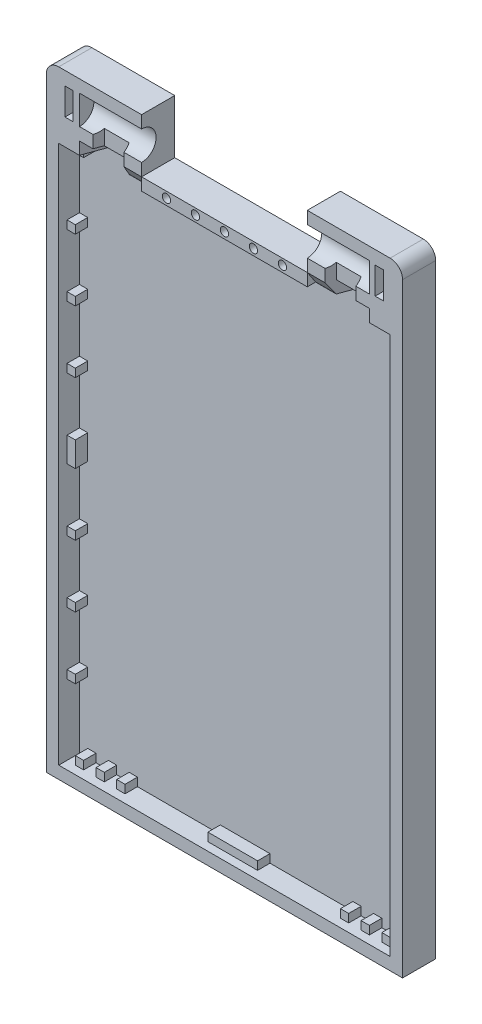
SolidWorks part; units mm, degrees
material "ABS"
ref_plane "Ön Düzlem" through (0, 0, 0) normal (0, 0, 1) x (1, 0, 0)
ref_plane "Üst Düzlem" through (0, 0, 0) normal (0, 1, 0) x (1, 0, 0)
ref_plane "Sağ Düzlem" through (0, 0, 0) normal (1, 0, 0) x (0, 0, -1)
sketch "Çizim1" plane through (0, 0, 0) normal (0, 0, 1) x (1, 0, 0)
  line L0 (-27.9937, 101.5335) -> (-27.9937, -28.4665)
  line L1 (-27.9937, 101.5335) -> (-22.9937, 101.5335)
  line L2 (52.0063, 101.5335) -> (52.0063, -28.4665)
  line L3 (-27.9937, -28.4665) -> (52.0063, -28.4665)
  line L4 (-30.9937, -31.4665) -> (55.0063, -31.4665)
  line L5 (55.0063, 104.5335) -> (55.0063, -31.4665)
  line L6 (-27.9937, 104.5335) -> (-22.9937, 104.5335)
  line L7 (-30.9937, 104.5335) -> (-30.9937, -31.4665)
  line L8 (-30.9937, 104.5335) -> (-30.9937, 114.5335)
  line L10 (55.0063, 114.5335) -> (55.0063, 104.5335)
  line L11 (-27.9937, 104.5335) -> (-27.9937, 117.5335)
  line L12 (-27.9937, 117.5335) -> (-7.9937, 117.5335)
  line L13 (52.0063, 117.5335) -> (52.0063, 104.5335)
  line L14 (-7.9937, 104.5335) -> (32.0063, 104.5335)
  line L15 (37.0063, 104.5335) -> (37.0063, 101.5335)
  line L16 (-7.9937, 117.5335) -> (-7.9937, 104.5335)
  line L17 (32.0063, 117.5335) -> (32.0063, 104.5335)
  line L18 (32.0063, 104.5335) -> (37.0063, 104.5335)
  line L19 (-30.9937, 104.5335) -> (55.0063, 104.5335) construction
  line L20 (32.0063, 117.5335) -> (52.0063, 117.5335)
  line L21 (-27.9937, 117.5335) -> (52.0063, 117.5335) construction
  line L22 (47.0063, 104.5335) -> (47.0063, 101.5335)
  line L23 (-22.9937, 104.5335) -> (-12.9937, 104.5335)
  line L24 (37.0063, 104.5335) -> (47.0063, 104.5335)
  line L26 (-30.9937, 120.5335) -> (55.0063, 120.5335) construction
  line L27 (47.0063, 104.5335) -> (52.0063, 104.5335)
  line L28 (47.0063, 101.5335) -> (52.0063, 101.5335)
  line L29 (-27.9937, 101.5335) -> (52.0063, 101.5335) construction
  line L30 (-22.9937, 104.5335) -> (-22.9937, 101.5335)
  line L31 (-12.9937, 104.5335) -> (-12.9937, 101.5335)
  line L32 (-12.9937, 104.5335) -> (-7.9937, 104.5335)
  line L33 (-12.9937, 101.5335) -> (37.0063, 101.5335)
  line L35 (-30.9937, 104.5335) -> (-30.9937, 120.5335) construction
  line L37 (-26.4937, 114.2835) -> (-24.4937, 114.2835)
  line L38 (-26.4937, 114.2835) -> (-26.4937, 107.7835)
  line L39 (-24.4937, 114.2835) -> (-24.4937, 107.7835)
  line L41 (-26.4937, 107.7835) -> (-24.4937, 107.7835)
  line L43 (50.3892, 107.7835) -> (48.3892, 107.7835)
  line L44 (48.3892, 114.2835) -> (48.3892, 107.7835)
  line L45 (50.3892, 114.2835) -> (50.3892, 107.7835)
  line L46 (50.3892, 114.2835) -> (48.3892, 114.2835)
  line L47 (55.0063, 120.5335) -> (55.0063, 104.5335) construction
  arc A0 (-27.9937, 117.5335) -> (-30.9937, 114.5335) centre (-27.9937, 114.5335) ccw
  arc A1 (52.0063, 117.5335) -> (55.0063, 114.5335) centre (52.0063, 114.5335) cw
extrude "Yükseklik-Ekstrüzyon1" add sketch "Çizim1" along normal blind 8 contours L10 L13 L27 L22 L28 L2 L3 L0 L1 L30 L6 L11 L8 L7 L4 L5 region at (-29.7141, 36.5335, 0)
extrude "Yükseklik-Ekstrüzyon3" add sketch "Çizim1<4>" along normal blind 8 contours L23 L32 L16 L12 L11 L6 | L24 L27 L13 L20 L17 L18 region at (-17.5989, 111.0335, 0) region at (41.6178, 111.0335, 0)
sketch "Çizim1<4>" plane through (0, 0, 0) normal (0, 0, 1) x (1, 0, 0) same geometry as "Çizim1"
extrude "Yükseklik-Ekstrüzyon4" add sketch "Çizim1<6>" along normal blind 3 contours L33 L31 L23 L30 L1 L0 L3 L2 L28 L22 L24 L15 region at (12.0063, 36.9149, 0)
sketch "Çizim1<6>" plane through (0, 0, 0) normal (0, 0, 1) x (1, 0, 0) same geometry as "Çizim1"
extrude "Yükseklik-Ekstrüzyon5" add sketch "Çizim1<7>" along normal blind 6 contours L31 L33 L15 L18 L14 L32 region at (12.0063, 103.0335, 0)
sketch "Çizim1<7>" plane through (0, 0, 0) normal (0, 0, 1) x (1, 0, 0) same geometry as "Çizim1"
sketch "Çizim2" plane through (32.0063, 0, 0) normal (-1, 0, 0) x (0, 0, 1)
  line L0 (8, 117.5335) -> (8, 114.5335)
  line L1 (8, 117.5335) -> (8, 104.5335) construction
  line L4 (8, 104.5335) -> (8, 107.5335)
  line L5 (8, 114.5335) -> (8, 107.5335)
  arc A0 (8, 114.5335) -> (8, 107.5335) centre (8, 111.0335) ccw
  line M4 (8, 104.5335) -> (8, 117.5335)
extrude "Kes-Ekstrüzyon1" cut sketch "Çizim2" against normal blind 15 contours A0 M4 region at (32.0063, 111.0335, 6.5146)
extrude "Kes-Ekstrüzyon2" cut sketch "Çizim2<3>" along normal blind 55 contours A0 M4 region at (32.0063, 111.0335, 6.5146)
sketch "Çizim2<3>" plane through (32.0063, 0, 0) normal (-1, 0, 0) x (0, 0, 1) same geometry as "Çizim2"
sketch "Çizim7" plane through (0, 0, 8) normal (0, 0, 1) x (1, 0, 0)
  line L1 (-12.9937, 104.5335) -> (-18.9937, 104.5335)
  line L2 (-12.9937, 104.5335) -> (-12.9937, 108.5335)
  line L3 (-12.9937, 108.5335) -> (-18.9937, 108.5335)
  line L4 (-18.9937, 104.5335) -> (-18.9937, 108.5335)
  line L7 (37.0063, 108.5335) -> (43.0063, 108.5335)
  line L8 (37.0063, 104.5335) -> (37.0063, 108.5335)
  line L9 (37.0063, 104.5335) -> (43.0063, 104.5335)
  line L10 (43.0063, 104.5335) -> (43.0063, 108.5335)
extrude "Kes-Ekstrüzyon5" cut sketch "Çizim7" against normal blind 2
ref_plane "Düzlem3" through (37.0063, 101.5335, 3) normal (0, -1, 0) x (-1, 0, 0)
chamfer "Pah1" distance 3 angle 20 1 edges at (37.0063, 103.0335, 3) first distance on face at (37.0063, 103.0335, 4.5)
chamfer "Pah2" distance 3 angle 20 1 edges at (-12.9937, 103.0335, 3) first distance on face at (-12.9937, 103.0335, 4.5)
chamfer "Pah3" distance 5 angle 20 2 edges at (47.0063, 103.0335, 3) (-22.9937, 103.0335, 3) first distance on face at (47.0063, 103.0335, 5.5) first distance on face at (-22.9937, 103.0335, 5.5)
chamfer "Pah4" distance 2 angle 20 4 edges at (37.0063, 106.0335, 8) (43.0063, 106.0335, 8) (-18.9937, 106.0335, 8) (-12.9937, 106.0335, 8) first distance on face at (37.0063, 106.1521, 6.988) first distance on face at (43.0063, 106.1521, 6.988) first distance on face at (-18.9937, 106.1521, 6.988) first distance on face at (-12.9937, 106.1521, 6.988)
chamfer "Pah5" distance 2 angle 56 2 edges at (-10.4937, 104.5335, 6) (34.5063, 104.5335, 6) first distance on face at (-10.3117, 104.5335, 7) first distance on face at (34.3243, 104.5335, 7)
sketch "Çizim11" plane through (0, 0, 6) normal (0, 0, 1) x (1, 0, 0)
  line L0 (-7.9937, 104.5335) -> (-7.9937, 101.5335)
  line L1 (-7.9937, 104.5335) -> (32.0063, 104.5335)
  line L5 (-12.9937, 101.5335) -> (37.0063, 101.5335) construction
  line L6 (-7.9937, 101.5335) -> (32.0063, 101.5335)
  line L7 (32.0063, 101.5335) -> (32.0063, 104.5335)
  circle A0 centre (12.0063, 103.0509) radius 1
  circle A1 centre (19.0063, 103.0509) radius 1
  circle A2 centre (26.0063, 103.0509) radius 1
  circle A3 centre (12.0063, 103.0509) radius 1
  circle A4 centre (19.0063, 103.0509) radius 1
  circle A5 centre (5.0063, 103.0509) radius 1
  circle A6 centre (12.0063, 103.0509) radius 1
  circle A7 centre (5.0063, 103.0509) radius 1
  circle A8 centre (-1.9937, 103.0509) radius 1
  line M1 (32.0063, 104.5335) -> (-7.9937, 104.5335)
  line M2 (-7.9937, 104.5335) -> (-7.9937, 101.5683)
  line M5 (-12.9937, 101.5335) -> (37.0063, 101.5335)
  line M8 (32.0063, 101.5683) -> (32.0063, 104.5335)
  dimension "D1" = 3
  dimension "D2" = 3
extrude "Yükseklik-Ekstrüzyon10" add sketch "Çizim11" along normal up to surface (2 mm away) contours L7 L0 A8 A5 A2 A1 A0 M5 M8 M1 M2 region at (12.0063, 104.1323, 6) up to face at (-10.1297, 106.0335, 8)
sketch "Çizim12" plane through (0, 0, 3) normal (0, 0, 1) x (1, 0, 0)
  line L1 (-25.9937, 101.5335) -> (-23.9937, 101.5335)
  line L7 (-25.9937, 99.5335) -> (-23.9937, 99.5335)
  line L9 (-25.9937, 99.5335) -> (-25.9937, 101.5335)
  line L10 (-25.9937, 101.5335) -> (-23.9937, 101.5335)
  line L11 (-23.9937, 101.5335) -> (-23.9937, 99.5335)
  line L12 (-23.9937, 99.5335) -> (-25.9937, 99.5335)
  line L16 (-27.9937, 39.5335) -> (-27.9937, 33.5335)
  line L46 (-25.9937, 99.5335) -> (50.0063, 99.5335) construction
  line L47 (-27.9937, 101.5335) -> (52.0063, 101.5335)
  line L48 (-27.9937, -28.4665) -> (52.0063, -28.4665) construction
  line L49 (-25.9937, 33.5335) -> (-25.9937, 39.5335)
  line L50 (6.0063, -26.4665) -> (18.0063, -26.4665)
  line L51 (50.0063, 84.5335) -> (50.0063, 82.5335)
  line L52 (50.0063, 69.5335) -> (50.0063, 67.5335)
  line L53 (52.0063, 69.5335) -> (52.0063, 67.5335)
  line L54 (52.0063, 54.5335) -> (52.0063, 52.5335)
  line L55 (50.0063, 54.5335) -> (50.0063, 52.5335)
  line L56 (50.0063, 39.5335) -> (50.0063, 33.5335)
  line L57 (52.0063, 33.5335) -> (52.0063, 39.5335)
  line L58 (-25.9937, 84.5335) -> (-25.9937, 82.5335)
  line L59 (-25.9937, 82.5335) -> (-27.9937, 82.5335)
  line L60 (-27.9937, 82.5335) -> (-27.9937, 84.5335)
  line L61 (-27.9937, 84.5335) -> (-25.9937, 84.5335)
  line L62 (-25.9937, 69.5335) -> (-25.9937, 67.5335)
  line L63 (-25.9937, 67.5335) -> (-27.9937, 67.5335)
  line L64 (-27.9937, 67.5335) -> (-27.9937, 69.5335)
  line L65 (-27.9937, 69.5335) -> (-25.9937, 69.5335)
  line L66 (-25.9937, 54.5335) -> (-25.9937, 52.5335)
  line L67 (-25.9937, 52.5335) -> (-27.9937, 52.5335)
  line L68 (-27.9937, 52.5335) -> (-27.9937, 54.5335)
  line L69 (-27.9937, 54.5335) -> (-25.9937, 54.5335)
  line L73 (-27.9937, 39.5335) -> (-25.9937, 39.5335)
  line L90 (-27.9937, 84.5335) -> (-27.9937, 82.5335)
  line L91 (-27.9937, 101.5335) -> (-27.9937, -28.4665) construction
  line L92 (-27.9937, 101.5335) -> (52.0063, 101.5335) construction
  line L93 (6.0063, -26.4665) -> (6.0063, -28.4665)
  line L94 (6.0063, -28.4665) -> (18.0063, -28.4665)
  line L95 (18.0063, -26.4665) -> (18.0063, -28.4665)
  line L96 (-27.9937, 101.5335) -> (-27.9937, -28.4665)
  line L97 (52.0063, 84.5335) -> (52.0063, 82.5335)
  line L98 (52.0063, 101.5335) -> (52.0063, -28.4665) construction
  line L99 (50.0063, 99.5335) -> (50.0063, -26.4665) construction
  line L100 (-25.9937, -26.4665) -> (50.0063, -26.4665) construction
  line L101 (-27.9937, -28.4665) -> (52.0063, -28.4665) construction
  line L102 (-25.9937, 99.5335) -> (-25.9937, -26.4665) construction
  line L103 (52.0063, 39.5335) -> (50.0063, 39.5335)
  line L104 (-27.9937, -28.4665) -> (52.0063, -28.4665)
  line L105 (52.0063, 101.5335) -> (52.0063, -28.4665)
  line L107 (52.0063, 54.5335) -> (50.0063, 54.5335)
  line L108 (52.0063, 52.5335) -> (52.0063, 54.5335)
  line L109 (50.0063, 52.5335) -> (52.0063, 52.5335)
  line L110 (50.0063, 54.5335) -> (50.0063, 52.5335)
  line L113 (-25.9937, 54.5335) -> (-25.9937, 52.5335)
  line L114 (-27.9937, 54.5335) -> (-27.9937, 52.5335)
  line L115 (-27.9937, 69.5335) -> (-27.9937, 67.5335)
  line L116 (-25.9937, 69.5335) -> (-25.9937, 67.5335)
  line L117 (-25.9937, 84.5335) -> (-25.9937, 82.5335)
  line L124 (52.0063, 69.5335) -> (50.0063, 69.5335)
  line L125 (52.0063, 67.5335) -> (52.0063, 69.5335)
  line L126 (50.0063, 67.5335) -> (52.0063, 67.5335)
  line L127 (50.0063, 69.5335) -> (50.0063, 67.5335)
  line L128 (52.0063, 84.5335) -> (50.0063, 84.5335)
  line L129 (52.0063, 82.5335) -> (52.0063, 84.5335)
  line L130 (50.0063, 82.5335) -> (52.0063, 82.5335)
  line L131 (50.0063, 84.5335) -> (50.0063, 82.5335)
  line L142 (48.0063, 99.5335) -> (50.0063, 99.5335)
  line L143 (48.0063, 101.5335) -> (48.0063, 99.5335)
  line L144 (50.0063, 101.5335) -> (48.0063, 101.5335)
  line L145 (50.0063, 99.5335) -> (50.0063, 101.5335)
  line L146 (50.0063, 99.5335) -> (48.0063, 99.5335)
  line L147 (50.0063, 101.5335) -> (48.0063, 101.5335)
  line L148 (-25.9937, -11.4665) -> (-25.9937, -9.4665)
  line L149 (-25.9937, 3.5335) -> (-25.9937, 5.5335)
  line L150 (-27.9937, 3.5335) -> (-27.9937, 5.5335)
  line L151 (-27.9937, 18.5335) -> (-27.9937, 20.5335)
  line L152 (-25.9937, 18.5335) -> (-25.9937, 20.5335)
  line L155 (-15.9937, -28.4665) -> (-13.9937, -28.4665)
  line L156 (-20.9937, -28.4665) -> (-18.9937, -28.4665)
  line L157 (-27.9937, -11.4665) -> (-27.9937, -9.4665)
  line L158 (-27.9937, 33.5335) -> (-25.9937, 33.5335)
  line L162 (-27.9937, 18.5335) -> (-25.9937, 18.5335)
  line L163 (-27.9937, 20.5335) -> (-27.9937, 18.5335)
  line L164 (-25.9937, 20.5335) -> (-27.9937, 20.5335)
  line L165 (-25.9937, 18.5335) -> (-25.9937, 20.5335)
  line L166 (-27.9937, 3.5335) -> (-25.9937, 3.5335)
  line L167 (-27.9937, 5.5335) -> (-27.9937, 3.5335)
  line L168 (-25.9937, 5.5335) -> (-27.9937, 5.5335)
  line L169 (-25.9937, 3.5335) -> (-25.9937, 5.5335)
  line L170 (-27.9937, -11.4665) -> (-25.9937, -11.4665)
  line L171 (-27.9937, -9.4665) -> (-27.9937, -11.4665)
  line L172 (-25.9937, -9.4665) -> (-27.9937, -9.4665)
  line L173 (-25.9937, -11.4665) -> (-25.9937, -9.4665)
  line L174 (-15.9937, -26.4665) -> (-13.9937, -26.4665)
  line L175 (-20.9937, -26.4665) -> (-18.9937, -26.4665)
  line L176 (-13.9937, -26.4665) -> (-15.9937, -26.4665)
  line L177 (-13.9937, -28.4665) -> (-13.9937, -26.4665)
  line L178 (-15.9937, -28.4665) -> (-13.9937, -28.4665)
  line L179 (-15.9937, -26.4665) -> (-15.9937, -28.4665)
  line L180 (-18.9937, -26.4665) -> (-20.9937, -26.4665)
  line L181 (-18.9937, -28.4665) -> (-18.9937, -26.4665)
  line L182 (-20.9937, -28.4665) -> (-18.9937, -28.4665)
  line L183 (-20.9937, -26.4665) -> (-20.9937, -28.4665)
  line L184 (-23.9937, -26.4665) -> (-25.9937, -26.4665)
  line L185 (-23.9937, -28.4665) -> (-23.9937, -26.4665)
  line L186 (-25.9937, -28.4665) -> (-23.9937, -28.4665)
  line L187 (-25.9937, -26.4665) -> (-25.9937, -28.4665)
  line L188 (-25.9937, -26.4665) -> (-23.9937, -26.4665)
  line L189 (-25.9937, -28.4665) -> (-23.9937, -28.4665)
  line L190 (50.0063, -28.4665) -> (48.0063, -28.4665)
  line L191 (50.0063, -26.4665) -> (48.0063, -26.4665)
  line L192 (50.0063, -26.4665) -> (50.0063, -28.4665)
  line L193 (50.0063, -28.4665) -> (48.0063, -28.4665)
  line L194 (48.0063, -28.4665) -> (48.0063, -26.4665)
  line L195 (48.0063, -26.4665) -> (50.0063, -26.4665)
  line L196 (45.0063, -26.4665) -> (45.0063, -28.4665)
  line L197 (45.0063, -28.4665) -> (43.0063, -28.4665)
  line L198 (43.0063, -28.4665) -> (43.0063, -26.4665)
  line L199 (43.0063, -26.4665) -> (45.0063, -26.4665)
  line L200 (40.0063, -26.4665) -> (40.0063, -28.4665)
  line L201 (40.0063, -28.4665) -> (38.0063, -28.4665)
  line L202 (38.0063, -28.4665) -> (38.0063, -26.4665)
  line L203 (38.0063, -26.4665) -> (40.0063, -26.4665)
  line L204 (45.0063, -26.4665) -> (43.0063, -26.4665)
  line L205 (40.0063, -26.4665) -> (38.0063, -26.4665)
  line L206 (50.0063, -11.4665) -> (50.0063, -9.4665)
  line L207 (50.0063, -9.4665) -> (52.0063, -9.4665)
  line L208 (52.0063, -9.4665) -> (52.0063, -11.4665)
  line L209 (52.0063, -11.4665) -> (50.0063, -11.4665)
  line L210 (50.0063, 3.5335) -> (50.0063, 5.5335)
  line L211 (50.0063, 5.5335) -> (52.0063, 5.5335)
  line L212 (52.0063, 5.5335) -> (52.0063, 3.5335)
  line L213 (52.0063, 3.5335) -> (50.0063, 3.5335)
  line L214 (50.0063, 18.5335) -> (50.0063, 20.5335)
  line L215 (50.0063, 20.5335) -> (52.0063, 20.5335)
  line L216 (52.0063, 20.5335) -> (52.0063, 18.5335)
  line L217 (52.0063, 18.5335) -> (50.0063, 18.5335)
  line L221 (52.0063, 33.5335) -> (50.0063, 33.5335)
  line L222 (52.0063, -11.4665) -> (52.0063, -9.4665)
  line L223 (45.0063, -28.4665) -> (43.0063, -28.4665)
  line L224 (40.0063, -28.4665) -> (38.0063, -28.4665)
  line L227 (50.0063, 18.5335) -> (50.0063, 20.5335)
  line L228 (52.0063, 18.5335) -> (52.0063, 20.5335)
  line L229 (52.0063, 3.5335) -> (52.0063, 5.5335)
  line L230 (50.0063, 3.5335) -> (50.0063, 5.5335)
  line L231 (50.0063, -11.4665) -> (50.0063, -9.4665)
  line M72 (-21.1738, 101.5335) -> (-27.9937, 101.5335)
  line M73 (-27.9937, 101.5335) -> (-27.9937, -28.4665)
  line M74 (-27.9937, -28.4665) -> (52.0063, -28.4665)
  line M75 (52.0063, -28.4665) -> (52.0063, 101.5335)
extrude "Yükseklik-Ekstrüzyon12" add sketch "Çizim12" along normal blind 3 contours L158 L49 L73 M73 | L69 L67 L66 M73 | L65 L63 L62 M73 | L61 L59 L58 M73 | L11 L9 L7 M72 | L142 L145 L47 L143 | L51 L130 L128 M75 | L52 L126 L124 M75 | L55 L109 L107 M75 | L221 L103 L56 M75 | L217 L105 L215 L214 | L213 L211 L210 M75 | L209 L105 L207 L206 | L194 L104 L192 L191 | L199 L198 L104 L196 | L203 L202 L104 L200 | L95 L50 L93 M74 | L174 L179 L104 L177 | L175 L183 L104 L181 | L184 L187 L104 L185 | L148 L172 L96 L170 | L149 L168 L96 L166 | L152 L164 L96 L162 region at (-24.9937, 100.5335, 3) region at (-26.9937, 83.5335, 3) region at (49.0063, 100.5335, 3) region at (-26.9937, 68.5335, 3) region at (51.0063, 83.5335, 3) region at (-26.9937, 53.5335, 3) region at (51.0063, 68.5335, 3) region at (-26.9937, 36.5335, 3) region at (51.0063, 53.5335, 3) region at (-26.9937, 19.5335, 3) region at (51.0063, 36.5335, 3) region at (-26.9937, 4.5335, 3) region at (51.0063, 19.5335, 3) region at (-26.9937, -10.4665, 3) region at (51.0063, 4.5335, 3) region at (-24.9937, -27.4665, 3) region at (51.0063, -10.4665, 3) region at (-19.9937, -27.4665, 3) region at (49.0063, -27.4665, 3) region at (-14.9937, -27.4665, 3) region at (44.0063, -27.4665, 3) region at (12.0063, -27.4665, 3) region at (39.0063, -27.4665, 3)
